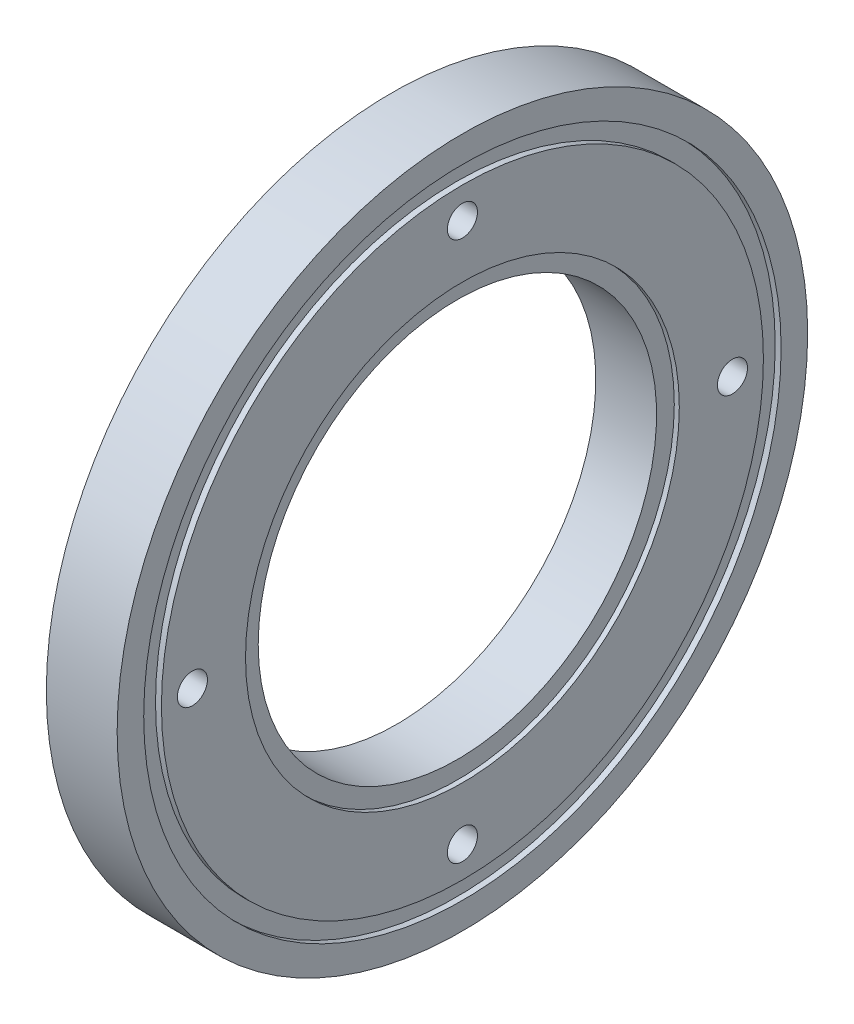
SolidWorks part; units mm, degrees
ref_plane "Front Plane" through (0, 0, 0) normal (0, 0, 1) x (1, 0, 0)
ref_plane "Top Plane" through (0, 0, 0) normal (0, 1, 0) x (1, 0, 0)
ref_plane "Right Plane" through (0, 0, 0) normal (1, 0, 0) x (0, 0, -1)
sketch "Sketch1" plane through (0, 0, 0) normal (0, 0, 1) x (1, 0, 0)
  line L0 (-801.9206, 0) -> (36107.5283, 0) construction
  line L10 (21.0477, 24.5) -> (21.0477, 39)
  line L12 (21.0477, 39) -> (13.0477, 39)
  line L16 (21.0477, 24.5) -> (20.4817, 24.5)
  line L17 (20.4817, 24.5) -> (20.4817, 22.5)
  line L18 (13.0477, 39) -> (13.0477, 24.5)
  line L22 (18.4817, 22.5) -> (20.4817, 22.5)
  line L28 (13.0477, 24.5) -> (13.6137, 24.5)
  line L29 (13.6137, 24.5) -> (13.6137, 22.5)
  line L30 (13.6137, 22.5) -> (18.4817, 22.5)
  line L31 (21.0477, 36) -> (20.3807, 36)
  line L32 (20.3807, 36) -> (20.3807, 34)
  line L33 (20.3807, 34) -> (21.0477, 34)
  line L34 (13.0477, 36) -> (13.7147, 36)
  line L35 (13.7147, 36) -> (13.7147, 34)
  line L36 (13.7147, 34) -> (13.0477, 34)
  dimension "D1" = 8
  dimension "D5" = 39
  dimension "D2" = 36
  dimension "D3" = 0.566
  dimension "D4" = 2
  dimension "D6" = 0.667
  dimension "D8" = 24.5
  dimension "D9" = 2
  dimension "D10" = 2
revolve "Revolve17" add sketch "Sketch1" angle 360 about L0 region at (17.0477, 30.7899, 0)
sketch "Sketch4" plane through (13.0477, 0, 0) normal (-1, 0, 0) x (0, 0, 1)
  circle A0 centre (0, 0) radius 30.5 construction
  point P3 (0, 30.5)
  point P7 (30.5, 0)
  point P12 (-30.5, 0)
  point P13 (0, -30.5)
  point P19 (0, 0)
  point P20 (0, 30.9019)
  point P21 (30.9019, 0)
  point P22 (0, -30.9019)
  point P23 (-28.325, 0)
  point P24 (-30.9019, 0)
  dimension "D1" = 61
hole_wizard "M3 Clearance Hole1" positions "Sketch4" profile "Sketch5" hole size "M3" standard "ISO"
sketch "Sketch5" plane through (13.0477, -30.5, 0) normal (0, 1, 0) x (0, 0, 1)
  line L0 (0, 0) -> (0, 9.0215)
  line L1 (0, 9.0215) -> (1.7, 8)
  line L2 (1.7, 8) -> (1.7, 0)
  line L5 (1.7, 0) -> (0, 0)
  line L10 (0, 9.0215) -> (-1.7, 8) construction
  line L11 (0, -6.35) -> (0, 107.95) construction
  dimension "Hole Dia." = 3.4
  dimension "Hole Depth" = 8
  dimension "Drill Angle" = 118
